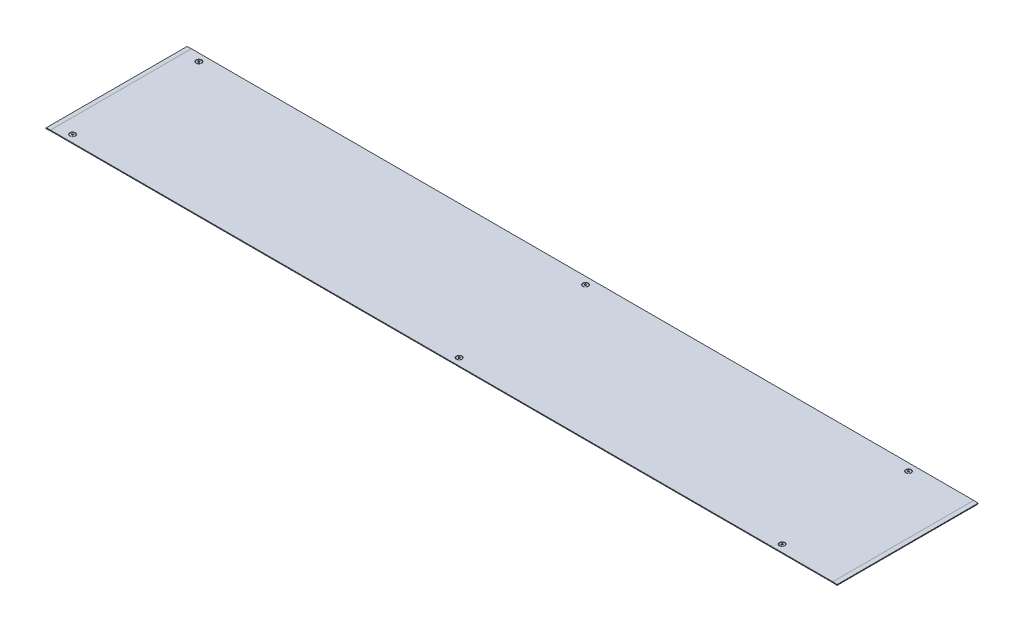
SolidWorks part; units mm, degrees
ref_plane "Front Plane" through (0, 0, 0) normal (0, 0, 1) x (1, 0, 0)
ref_plane "Top Plane" through (0, 0, 0) normal (0, 1, 0) x (1, 0, 0)
ref_plane "Right Plane" through (0, 0, 0) normal (1, 0, 0) x (0, 0, -1)
ref_axis "Axis1" through (-33.252, 0, 0) along (1, 0, 0)
ref_plane "Plane1" through (1000, 0, 0) normal (1, 0, 0) x (0, 0, -1)
ref_plane "Plane2" through (500, 0, 0) normal (1, 0, 0) x (0, 0, -1)
sketch "Sketch1" plane through (0, 0, 0) normal (0, 0, 1) x (1, 0, 0)
  line L0 (15.3, 14.6154) -> (15.3698, 13.6178)
  line L1 (15.3698, 13.6178) -> (20.8349, 14)
  line L2 (20.8349, 14) -> (981.0051, 14)
  line L3 (1000, -25.0335) -> (1000, 25.0335) construction
  line L5 (981.04, 15) -> (986.34, 14.6294)
  line L6 (981.04, 15) -> (20.8, 15)
  line L7 (20.8, 15) -> (15.3, 14.6154)
  line L8 (95.15, 0) -> (-95.15, 0) construction
  line L10 (986.2702, 13.6318) -> (981.0051, 14)
  line L11 (986.34, 14.6294) -> (986.2702, 13.6318)
  line L20 (0, -3.3) -> (0, 3.3) construction
  dimension "FIX_6" = 5.3
  dimension "FIX_1" = 15
  dimension "FIX_5" = 5.5
  dimension "FIX_4" = 15.3
  dimension "FIX_7" = 13.66
extrude "Boss-Extrude1" add sketch "Sketch1" along normal mid plane 173
ref_plane "Plane3" through (39, 0, 0) normal (1, 0, 0) x (0, 0, -1)
ref_plane "Plane4" through (910, 0, 0) normal (1, 0, 0) x (0, 0, -1)
ref_plane "Plane5" through (513.5, 0, 0) normal (1, 0, 0) x (0, 0, -1)
ref_plane "Plane6" through (0, 0, 77.5) normal (0, 0, 1) x (1, 0, 0)
sketch "Sketch3" plane through (0, 0, 77.5) normal (0, 0, 1) x (1, 0, 0)
  line L0 (39, 15) -> (42.5, 15)
  line L1 (981.04, 15) -> (20.8, 15) construction
  line L2 (42.5, 15) -> (41.5, 14)
  line L3 (39, 15) -> (39, 14) construction
  line L4 (20.8349, 14) -> (981.0051, 14) construction
  line L5 (41.5, 14) -> (39, 14)
  line L6 (39, -25.2809) -> (39, 25.2809) construction
  line L7 (39, 14) -> (39, 15)
  dimension "FIX_10" = 7
  dimension "FIX_11" = 45
revolve "Cut-Revolve1" cut sketch "Sketch3" angle 360 about L7
sketch "Sketch4" plane through (0, 0, 77.5) normal (0, 0, 1) x (1, 0, 0)
  line L0 (39, 15) -> (39, 9.3) construction
  line L1 (39, 14.8) -> (42, 14.8)
  line L2 (42, 14.8) -> (42, 14.5)
  line L3 (42, 14.5) -> (40.5, 13)
  line L4 (40.5, 13) -> (40.5, 9.3)
  line L5 (40.5, 9.3) -> (39, 9.3)
  line L6 (39, 14.8) -> (39, 9.3)
  line L7 (42.5, 15) -> (41.5, 14) construction
  dimension "FIX_15" = 3
  dimension "FIX_13" = 5.5
  dimension "FIX_16" = 6
  dimension "FIX_14" = 0.3
revolve "Revolve1" add sketch "Sketch4" angle 360 about L0
sketch "Sketch5" plane through (0, 14.8, 0) normal (0, 1, 0) x (1, 0, 0)
  line L0 (0, -3.3) -> (0, 3.3) construction
  line L1 (39, -76.3453) -> (38, -76.9226)
  line L2 (38, -76.9226) -> (38, -78.0774)
  line L3 (38, -78.0774) -> (39, -78.6547)
  line L4 (39, -78.6547) -> (40, -78.0774)
  line L5 (40, -78.0774) -> (40, -76.9226)
  line L6 (40, -76.9226) -> (39, -76.3453)
  circle A0 centre (39, -77.5) radius 1 construction
  dimension "FIX_18" = 2
extrude "Cut-Extrude1" cut sketch "Sketch5" against normal blind 1.2
ref_plane "Plane7" through (0, 11.4, 0) normal (0, 1, 0) x (1, 0, 0)
sketch "Sketch6" plane through (0, 11.4, 0) normal (0, 1, 0) x (1, 0, 0)
  line L0 (-3.3, 0) -> (3.3, 0) construction
  line L1 (35.8246, -77.5) -> (37.4123, -80.25)
  line L2 (37.4123, -80.25) -> (40.5877, -80.25)
  line L3 (40.5877, -80.25) -> (42.1754, -77.5)
  line L4 (42.1754, -77.5) -> (40.5877, -74.75)
  line L5 (40.5877, -74.75) -> (37.4123, -74.75)
  line L6 (37.4123, -74.75) -> (35.8246, -77.5)
  circle A0 centre (39, -77.5) radius 2.75 construction
  dimension "FIX_21" = 5.5
extrude "Boss-Extrude2" add sketch "Sketch6" against normal blind 2.4
mirror "Mirror1" about plane through (0, 0, 0) normal (0, 0, 1) of "Boss-Extrude2", "Cut-Extrude1", "Revolve1", "Cut-Revolve1"
pattern_linear "LPattern1" count 2 spacing 871 along (1, 0, 0) of "Cut-Revolve1", "Revolve1", "Cut-Extrude1", "Boss-Extrude2", "Mirror1"
pattern_linear "LPattern2" count 2 spacing 474.5 along (1, 0, 0) of "Cut-Revolve1", "Revolve1", "Cut-Extrude1", "Boss-Extrude2", "Mirror1"
equation "\"B\"=150"
equation "\"KSS_1@Boss-Extrude1\" = ( \"B\" + 25 ) - 2"
equation "\"KSS_2@Plane5\" = ( \"L@Plane1\" - \"FIX_8@Plane3\" - 12 ) / 2"
equation "\"KSS_3@Plane6\" = ( \"KSS_1@Boss-Extrude1\" - 18 ) / 2"
equation "\"KSS_4@LPattern1\" = \"L@Plane1\" - \"FIX_8@Plane3\" - \"FIX_9@Plane4\""
equation "\"KSS_5@LPattern2\"= \"KSS_2@Plane5\""
equation "\"LPattern2\"  = if ( \"L@Plane1\" < = 500 , \"suppressed\" , \"unsuppressed\" )"
